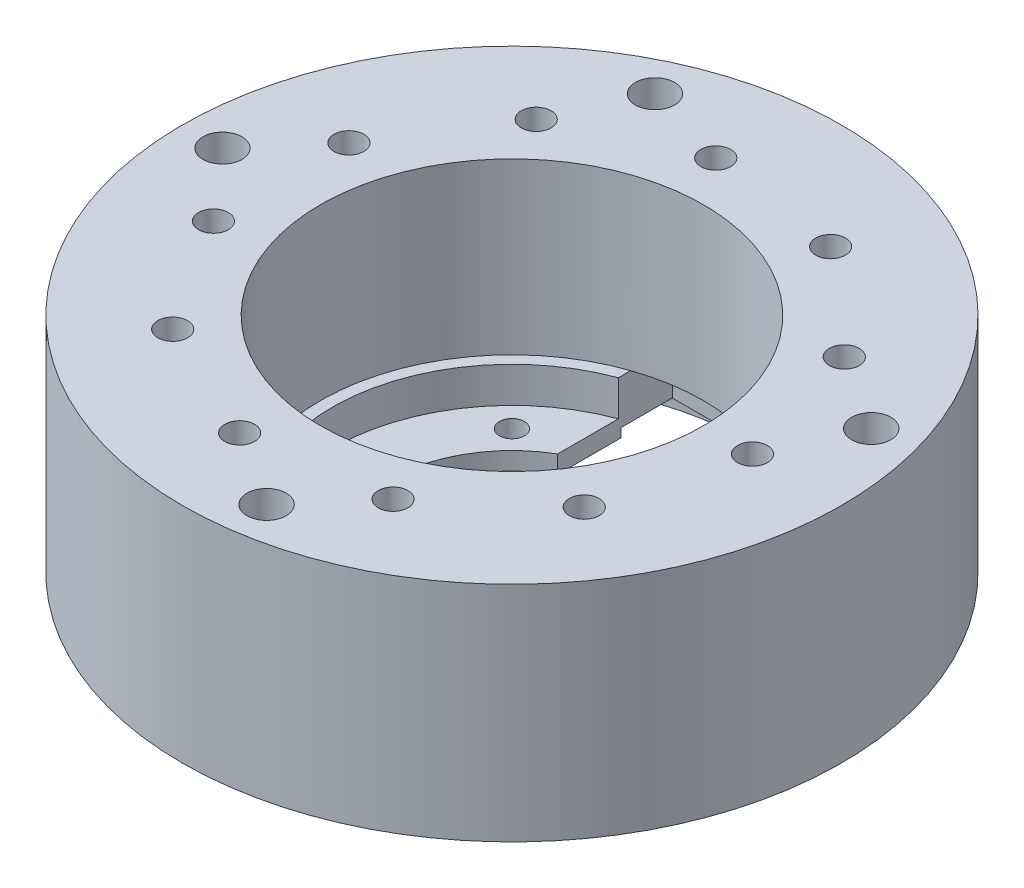
SolidWorks part; units mm, degrees
ref_plane "Front Plane" through (0, 0, 0) normal (0, 0, 1) x (1, 0, 0)
ref_plane "Top Plane" through (0, 0, 0) normal (0, 1, 0) x (1, 0, 0)
ref_plane "Right Plane" through (0, 0, 0) normal (1, 0, 0) x (0, 0, -1)
sketch "Sketch1" plane through (0, 0, 0) normal (0, 1, 0) x (1, 0, 0)
  circle A0 centre (0, 0) radius 37
  dimension "D1" = 74
extrude "Boss-Extrude1" add sketch "Sketch1" along normal blind 25.05
sketch "Sketch2" plane through (0, 25.05, 0) normal (0, 1, 0) x (1, 0, 0)
  circle A0 centre (0, 0) radius 21.5
  dimension "D1" = 43
extrude "Cut-Extrude1" cut sketch "Sketch2" against normal blind 19.05
sketch "Sketch3" plane through (0, 6, 0) normal (0, 1, 0) x (1, 0, 0)
  circle A0 centre (0, 0) radius 20.2
  dimension "D1" = 40.4
extrude "Cut-Extrude2" cut sketch "Sketch3" against normal blind 4
sketch "Sketch4" plane through (0, 2, 0) normal (0, 1, 0) x (1, 0, 0)
  circle A0 centre (0, 0) radius 14
  dimension "D1" = 28
extrude "Cut-Extrude3" cut sketch "Sketch4" against normal through all
sketch "Sketch5" plane through (0, 0, 0) normal (0, 1, 0) x (1, 0, 0)
  line L0 (0, -13.7775) -> (0, 13.7775) construction
  line L1 (-7, 11) -> (7, 11)
  line L2 (-7, 11) -> (-7, 25)
  line L3 (-7, 25) -> (7, 25)
  line L4 (7, 11) -> (7, 25)
  line L5 (-7, 11) -> (7, 25) construction
  line L6 (-7, 25) -> (7, 11) construction
  line L7 (-13.7775, 0) -> (13.7775, 0) construction
  point P0 (0, 18)
  dimension "D1" = 14
  dimension "D2" = 11
  dimension "D3" = 25
extrude "Cut-Extrude4" cut sketch "Sketch5" along normal blind 6
sketch "Sketch6" plane through (0, 0, 0) normal (0, 1, 0) x (1, 0, 0)
  line L0 (-13.7775, 0) -> (13.7775, 0) construction
  line L1 (0, -13.7775) -> (0, 13.7775) construction
  circle A0 centre (12.021, 12.021) radius 1.4
  circle A1 centre (12.021, -12.021) radius 1.4
  circle A2 centre (-12.021, -12.021) radius 1.4
  circle A3 centre (-12.021, 12.021) radius 1.4
  point P15 (0, 0)
  dimension "D1" = 2.8
  dimension "D2" = 12.021
  dimension "D3" = 12.021
  dimension "D4" = 4
extrude "Cut-Extrude5" cut sketch "Sketch6" along normal through all
sketch "Sketch7" plane through (0, 25.05, 0) normal (0, 1, 0) x (1, 0, 0)
  line L0 (-13.7775, 0) -> (13.7775, 0) construction
  line L1 (0, -13.7775) -> (0, 13.7775) construction
  circle A0 centre (27, 0) radius 1.675
  circle A1 centre (22.7138, -14.5973) radius 1.675
  circle A2 centre (11.2162, -24.5601) radius 1.675
  circle A3 centre (-3.8425, -26.7252) radius 1.675
  circle A4 centre (-17.6812, -20.4052) radius 1.675
  circle A5 centre (-25.9063, -7.6068) radius 1.675
  circle A6 centre (-25.9063, 7.6068) radius 1.675
  circle A7 centre (-17.6812, 20.4052) radius 1.675
  circle A8 centre (-3.8425, 26.7252) radius 1.675
  circle A9 centre (11.2162, 24.5601) radius 1.675
  circle A10 centre (22.7138, 14.5973) radius 1.675
  point P28 (0, 0)
  dimension "D1" = 3.35
  dimension "D2" = 27
  dimension "D3" = 11
extrude "Cut-Extrude6" cut sketch "Sketch7" against normal blind 4.75
sketch "Sketch8" plane through (0, 25.05, 0) normal (0, 1, 0) x (1, 0, 0)
  line L0 (0, 0) -> (43.2403, 0) construction
  line L1 (-13.7775, 0) -> (13.7775, 0) construction
  line L2 (0, 0) -> (44.2582, 12.9923) construction
  line L3 (0, 0) -> (-20.2523, 44.3371) construction
  line L4 (0, 0) -> (-46.5124, 0) construction
  line L5 (0, 0) -> (7.8044, -54.2928) construction
  circle A0 centre (31.1841, 9.1543) radius 2.2
  circle A1 centre (-13.5033, 29.562) radius 2.2
  circle A2 centre (-32.5, 0) radius 2.2
  circle A4 centre (4.6242, -32.1693) radius 2.2
  dimension "D5" = 4.4
  dimension "D7" = 4.4
  dimension "D9" = 4.4
  dimension "D11" = 4.4
  dimension "D1" = 16.36
  dimension "D2" = 114.55
  dimension "D3" = 180
  dimension "D4" = 278.18
  dimension "D6" = 32.5
  dimension "D8" = 32.5
  dimension "D10" = 32.5
  dimension "D12" = 32.5
extrude "Cut-Extrude7" cut sketch "Sketch8" against normal blind 5.5
sketch "Sketch9" plane through (0, 0, 0) normal (0, 1, 0) x (1, 0, 0)
  circle A0 centre (0, 0) radius 20.5
  circle A1 centre (0, 0) radius 26
  dimension "D1" = 52
  dimension "D2" = 41
extrude "Cut-Extrude8" cut sketch "Sketch9" along normal blind 1
sketch "Sketch11" plane through (0, 0, 0) normal (0, -1, 0) x (1, 0, 0)
  line L0 (0, 0) -> (29.2765, 29.2765) construction
  line L1 (13.7775, 0) -> (-13.7775, 0) construction
  circle A0 centre (21.9203, 21.9203) radius 2.2
  point P16 (0, -1.0607)
  dimension "D2" = 4.4
  dimension "D1" = 45
  dimension "D3" = 31
extrude "Cut-Extrude9" cut sketch "Sketch11" against normal blind 5.5
pattern_circular "CirPattern1" count 4 over 360 about axis through (0, 25.05, 0) along (0, -1, 0) of "Cut-Extrude9"
equation "\"pin_circle_R\" = 27"
equation "\"ecc\" = 1.5"
equation "\"n_pins\" = 11"
equation "\"pin_d\" = 3"
equation "\"out_pin_R\" = 18.5"
equation "\"disc_clr\" = 0.1"
equation "\"seat_6803\" = 26.02"
equation "\"seat_6806\" = 42.1"
equation "\"disc_t\" = 5"
equation "\"out_hole_clr\" = 0.7"
equation "\"boss_17\" = 17.15"
equation "\"rotor_bolt_R\" = 10"
equation "\"m25_clr\" = 2.8"
equation "\"m25_head\" = 5"
equation "\"insert_hole\" = 4.4"
equation "\"csk\" = 0.6"
equation "\"peg_d\" = 3.0"
equation "\"plug_d\" = 8.6"
equation "\"peg_clr\" = 0.3"
equation "\"m3_clr\" = 3.4"
equation "\"m3_head\" = 6.2"
equation "\"pin_press\" = 3.2"
equation "\"pin_slip\" = 3.35"
equation "\"hub_30\" = 30.20"
equation "\"hub_short\" = 0.2"
equation "\"m3_tap\" = 2.8"
equation "\"rear_plate_t\" = 2"
equation "\"motor_ring\" = 40.4"
equation "\"D1@Boss-Extrude1\"=\"rear_plate_t\" + 17.8 + 5.25"
equation "\"D1@Sketch6\"=\"m25_clr\""
equation "\"D1@Sketch7\"=\"pin_slip\""
equation "\"D2@Sketch7\"=\"pin_circle_R\""
equation "\"D5@Sketch8\"=\"insert_hole\""
equation "\"D7@Sketch8\"=\"insert_hole\""
equation "\"D9@Sketch8\"=\"insert_hole\""
equation "\"D11@Sketch8\"=\"insert_hole\""
equation "\"plug_shaft_d\" = 8.8"
equation "\"D2@Sketch11\"=\"insert_hole\""
